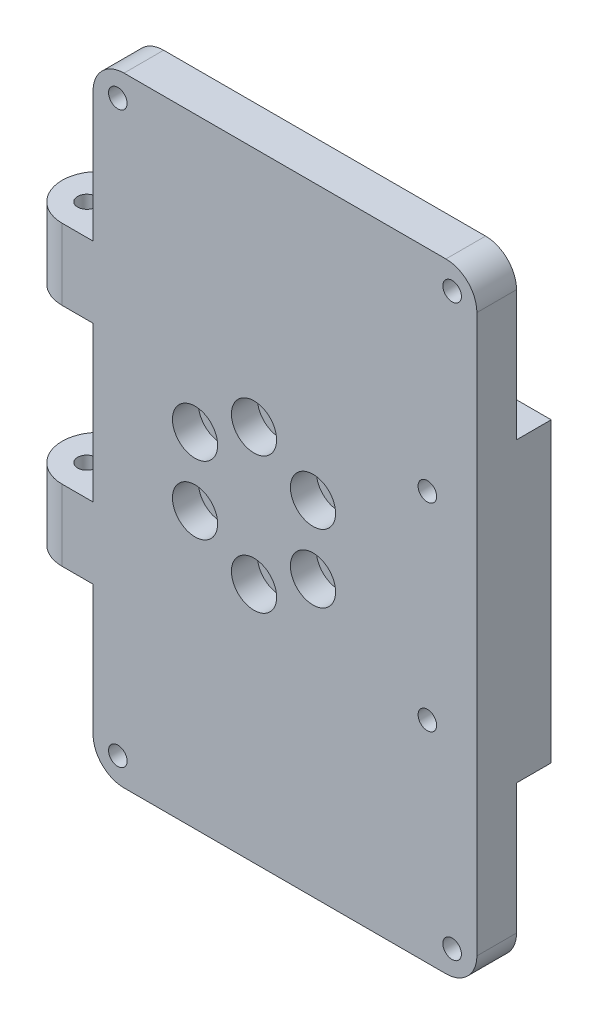
SolidWorks part; units mm, degrees
ref_plane "前视基准面" through (0, 0, 0) normal (0, 0, 1) x (1, 0, 0)
ref_plane "上视基准面" through (0, 0, 0) normal (0, 1, 0) x (1, 0, 0)
ref_plane "右视基准面" through (0, 0, 0) normal (1, 0, 0) x (0, 0, -1)
other "Configuration Table"
sketch "草图1" plane through (0, 0, 0) normal (0, 0, 1) x (1, 0, 0)
  line L1 (-36, 50) -> (36, 50)
  line L2 (-36, 50) -> (-36, -50)
  line L3 (-36, -50) -> (36, -50)
  line L4 (36, 50) -> (36, -50)
  line L5 (-36, 50) -> (36, -50) construction
  line L6 (-36, -50) -> (36, 50) construction
  point P0 (0, 0)
  dimension "D1" = 72
  dimension "D2" = 100
extrude "凸台-拉伸1" add sketch "草图1" along normal blind 12
sketch "草图2" plane through (0, 0, 0) normal (0, 0, -1) x (-1, 0, 0)
  line L0 (-32.0864, 0) -> (36.2456, 0) construction
  line L1 (-36, -50) -> (-36, 50) construction
  circle A0 centre (-28, 16) radius 1.5
  circle A1 centre (-28, -16) radius 1.5
  dimension "D1" = 3
  dimension "D3" = 32
  dimension "D4" = 8
  dimension "D2" = 2
extrude "切除-拉伸1" cut sketch "草图2" against normal blind 13
sketch "草图4" plane through (0, 0, 0) normal (0, 0, -1) x (-1, 0, 0)
  line L0 (-36, -50) -> (-36, 50) construction
  line L1 (-36, 50) -> (36, 50) construction
  circle A0 centre (-32, 46) radius 1.5
  circle A1 centre (22, 46) radius 1.5
  circle A2 centre (-32, -46) radius 1.5
  circle A3 centre (22, -46) radius 1.5
  dimension "D1" = 3
  dimension "D2" = 2
  dimension "D3" = 4
  dimension "D4" = 4
  dimension "D5" = 54
  dimension "D7" = 92
  dimension "D6" = 2
extrude "切除-拉伸3" cut sketch "草图4" against normal blind 15
sketch "草图5" plane through (0, 0, 0) normal (0, 0, -1) x (-1, 0, 0)
  circle A0 centre (0, 0) radius 14.5
  dimension "D1" = 29
extrude "凸台-拉伸2" add sketch "草图5" along normal blind 3.8
sketch "草图6" plane through (0, 0, -3.8) normal (0, 0, -1) x (-1, 0, 0)
  circle A0 centre (0, 0) radius 11 construction
  circle A1 centre (0, 11) radius 1.9
  circle A2 centre (9.5263, 5.5) radius 1.9
  circle A3 centre (9.5263, -5.5) radius 1.9
  circle A4 centre (0, -11) radius 1.9
  circle A5 centre (-9.5263, -5.5) radius 1.9
  circle A6 centre (-9.5263, 5.5) radius 1.9
  point P17 (0, 0)
  dimension "D1" = 22
  dimension "D2" = 3.8
  dimension "D3" = 6
extrude "切除-拉伸6" cut sketch "草图6" against normal blind 20
sketch "草图7" plane through (0, 0, 12) normal (0, 0, 1) x (1, 0, 0)
  circle A0 centre (0, 11) radius 3.65
  circle A1 centre (9.5263, 5.5) radius 3.65
  circle A2 centre (9.5263, -5.5) radius 3.65
  circle A3 centre (0, -11) radius 3.65
  circle A4 centre (-9.5263, -5.5) radius 3.65
  circle A5 centre (-9.5263, 5.5) radius 3.65
  point P15 (0, 0)
  dimension "D1" = 7.3
  dimension "D2" = 6
extrude "切除-拉伸7" cut sketch "草图7" against normal blind 4.2
sketch "草图8" plane through (0, 0, 0) normal (0, 0, -1) x (-1, 0, 0)
  circle A0 centre (-28, 16) radius 2.9
  circle A1 centre (-28, -16) radius 2.9
  dimension "D1" = 5.8
  dimension "D2" = 5.8
extrude "切除-拉伸8" cut sketch "草图8" against normal blind 3.2
sketch "草图9" plane through (0, 0, 0) normal (0, 0, -1) x (-1, 0, 0)
  line L0 (36, 50) -> (36, -50) construction
  line L1 (-36, 50) -> (36, 50)
  line L2 (-36, 50) -> (-36, 24)
  line L3 (-36, 24) -> (36, 24)
  line L4 (36, 50) -> (36, 24)
  line L6 (-36, -50) -> (36, -50)
  line L7 (-36, -50) -> (-36, -24)
  line L8 (-36, -24) -> (36, -24)
  line L9 (36, -50) -> (36, -24)
  dimension "D1" = 26
  dimension "D2" = 26
extrude "切除-拉伸9" cut sketch "草图9" against normal blind 5.6
fillet "圆角1" radius 5 4 edges at (36, -50, 8.8) (-36, -50, 8.8) (-36, 50, 8.8) (36, 50, 8.8)
sketch "草图10" plane through (0, 0, 0) normal (0, 0, -1) x (-1, 0, 0)
  line L0 (31, 50) -> (-31, 50) construction
  line L1 (36, -50) -> (26, -50)
  line L2 (36, -50) -> (36, 50)
  line L3 (36, 50) -> (26, 50)
  line L4 (26, -50) -> (26, 50)
  line L5 (36, 24) -> (36, 45) construction
  dimension "D1" = 100
  dimension "D2" = 10
  dimension "D3" = 10
extrude "切除-拉伸10" cut sketch "草图10" against normal blind 20
sketch "草图11" plane through (-26, 0, 0) normal (-1, 0, 0) x (0, 0, 1)
  line L0 (12, -50) -> (12, 50) construction
  line L1 (0, 24) -> (12, 24)
  line L2 (0, 24) -> (0, -24)
  line L3 (0, -24) -> (12, -24)
  line L4 (12, 24) -> (12, -24)
  dimension "D1" = 48
extrude "凸台-拉伸3" add sketch "草图11" along normal blind 11
sketch "草图12" plane through (0, -24, 0) normal (0, -1, 0) x (1, 0, 0)
  line L0 (-37, 0) -> (-37, 12) construction
  line L1 (-37, 12) -> (-26, 12) construction
  circle A0 centre (-32, 7) radius 1.5
  dimension "D1" = 3
  dimension "D2" = 5
  dimension "D3" = 5
extrude "切除-拉伸11" cut sketch "草图12" against normal blind 50
sketch "草图14" plane through (-37, 0, 0) normal (-1, 0, 0) x (0, 0, 1)
  line L0 (0, 24) -> (0, -24) construction
  line L1 (0, 12.5) -> (12, 12.5)
  line L2 (0, 12.5) -> (0, -12.5)
  line L3 (0, -12.5) -> (12, -12.5)
  line L4 (12, 12.5) -> (12, -12.5)
  line L5 (12, -24) -> (12, 24) construction
  dimension "D1" = 25
  dimension "D2" = 12.5
extrude "切除-拉伸12" cut sketch "草图14" against normal blind 11
fillet "圆角2" radius 6 4 edges at (-37, 18.25, 0) (-37, 18.25, 12) (-37, -18.25, 0) (-37, -18.25, 12)
fillet "圆角3" radius 5 2 edges at (-26, 50, 8.8) (-26, -50, 8.8)
